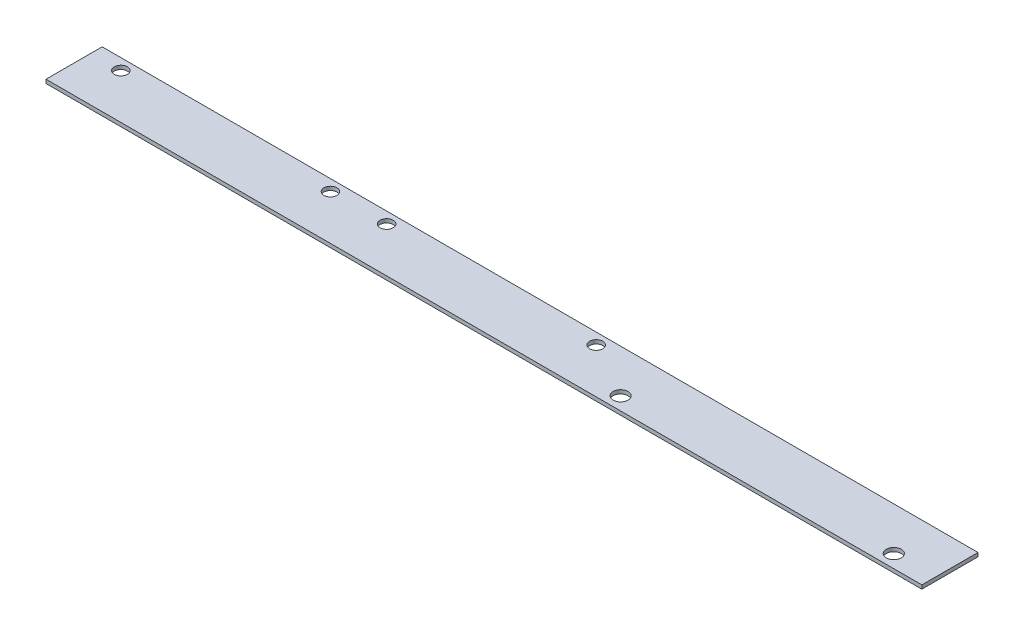
SolidWorks part; units mm, degrees
material "Простая углеродистая сталь"
ref_plane "Спереди" through (0, 0, 0) normal (0, 0, 1) x (1, 0, 0)
ref_plane "Сверху" through (0, 0, 0) normal (0, 1, 0) x (1, 0, 0)
ref_plane "Справа" through (0, 0, 0) normal (1, 0, 0) x (0, 0, -1)
sketch "Эскиз1" plane through (0, 0, 0) normal (0, 1, 0) x (1, 0, 0)
  line L1 (0, 0) -> (234, 0)
  line L2 (0, 0) -> (0, 15)
  line L3 (0, 15) -> (234, 15)
  line L4 (234, 0) -> (234, 15)
  circle A1 centre (150, 3.5) radius 2
  circle A2 centre (64, 12) radius 1.75
  circle A3 centre (8, 12) radius 1.75
  circle A4 centre (79, 12) radius 1.75
  circle A5 centre (135, 12) radius 1.75
  circle A8 centre (223, 3.5) radius 2
  dimension "D1" = 2
extrude "Бобышка-Вытянуть1" add sketch "Эскиз1" along normal blind 1
